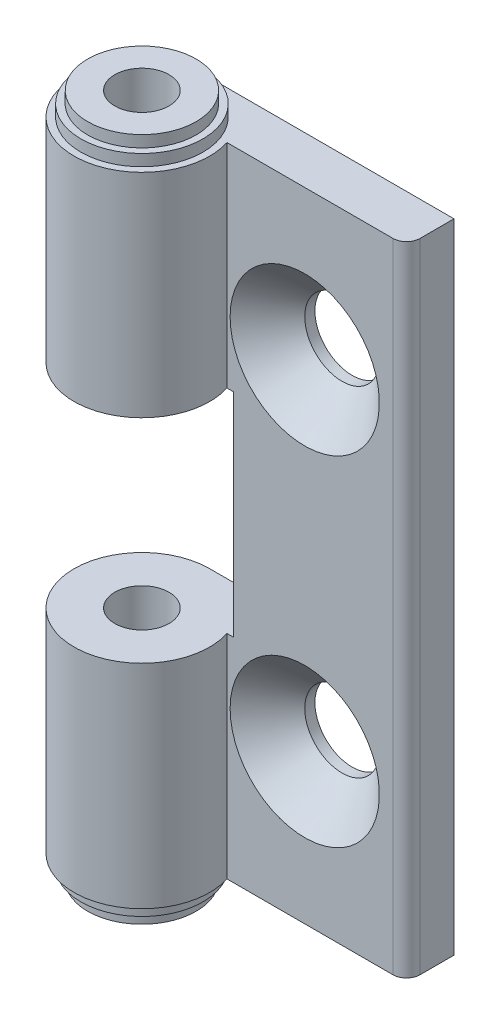
SolidWorks part; units mm, degrees
ref_plane "Front Plane" through (0, 0, 0) normal (0, 0, 1) x (1, 0, 0)
ref_plane "Top Plane" through (0, 0, 0) normal (0, 1, 0) x (1, 0, 0)
ref_plane "Right Plane" through (0, 0, 0) normal (1, 0, 0) x (0, 0, -1)
ref_plane "Plane1" through (0, 0, 0) normal (0, 0, 1) x (1, 0, 0)
sketch "Sketch1" plane through (0, 0, 0) normal (0, 0, 1) x (1, 0, 0)
  line L0 (0, 23.5) -> (5, 23.5)
  line L1 (5, 23.5) -> (5, -23.5)
  line L2 (5, -23.5) -> (0, -23.5)
  line L3 (0, -23.5) -> (0, 23.5)
  line L4 (0, -23.5) -> (0, 23.5) construction
revolve "Revolve1" add sketch "Sketch1" angle 360 about L4 reverse direction yes
ref_plane "Plane2" through (0, 0, -5) normal (0, 0, 1) x (1, 0, 0)
sketch "Sketch2" plane through (0, 0, -5) normal (0, 0, 1) x (1, 0, 0)
  line L0 (0, -23.5) -> (18, -23.5)
  line L1 (18, -23.5) -> (18, 23.5)
  line L2 (18, 23.5) -> (0, 23.5)
  line L3 (0, 23.5) -> (0, -23.5)
extrude "Boss-Extrude1" add sketch "Sketch2" along normal blind 3.5
ref_plane "Plane3" through (0, 0, 0) normal (0, 0, 1) x (1, 0, 0)
sketch "Sketch3" plane through (0, 0, 0) normal (0, 0, 1) x (1, 0, 0)
  line L0 (-47, -47) -> (47, -47)
  line L1 (47, -47) -> (47, 47)
  line L2 (47, 47) -> (-47, 47)
  line L3 (-47, 47) -> (-47, -47)
  line L4 (-5, 7.8333) -> (5.25, 7.8333)
  line L5 (5.25, 7.8333) -> (5.25, -7.8333)
  line L6 (5.25, -7.8333) -> (-5, -7.8333)
  line L7 (-5, -7.8333) -> (-5, -23.5)
  line L8 (-5, -23.5) -> (18, -23.5)
  line L9 (18, -23.5) -> (18, 23.5)
  line L10 (18, 23.5) -> (-5, 23.5)
  line L11 (-5, 23.5) -> (-5, 7.8333)
extrude "Cut-Extrude1" cut sketch "Sketch3" against normal blind 47 and the other way blind 47
ref_plane "Plane4" through (0, 0, 0) normal (0, 0, 1) x (1, 0, 0)
sketch "Sketch4" plane through (0, 0, 0) normal (0, 0, 1) x (1, 0, 0)
  line L0 (0, 25.2) -> (4, 25.2)
  line L1 (4, 25.2) -> (4, 24.35)
  line L2 (4, 24.35) -> (4.5, 24.35)
  line L3 (4.5, 24.35) -> (4.5, 23.5)
  line L4 (4.5, 23.5) -> (0, 23.5)
  line L5 (0, 23.5) -> (0, 25.2)
  line L6 (0, 23.5) -> (0, 25.2) construction
revolve "Revolve2" add sketch "Sketch4" angle 360 about L6 reverse direction yes
ref_plane "Plane5" through (0, 0, 0) normal (0, 0, 1) x (1, 0, 0)
sketch "Sketch5" plane through (0, 0, 0) normal (0, 0, 1) x (1, 0, 0)
  line L0 (0, -23.5) -> (4.5, -23.5)
  line L1 (4.5, -23.5) -> (4.5, -24.35)
  line L2 (4.5, -24.35) -> (4, -24.35)
  line L3 (4, -24.35) -> (4, -25.2)
  line L4 (4, -25.2) -> (0, -25.2)
  line L5 (0, -25.2) -> (0, -23.5)
  line L6 (0, -25.2) -> (0, -23.5) construction
revolve "Revolve3" add sketch "Sketch5" angle 360 about L6 reverse direction yes
ref_plane "Plane6" through (0, 0, 0) normal (0, 0, 1) x (1, 0, 0)
sketch "Sketch6" plane through (0, 0, 0) normal (0, 0, 1) x (1, 0, 0)
  line L0 (0, 26.7) -> (2, 26.7)
  line L1 (2, 26.7) -> (2, -26.7)
  line L2 (2, -26.7) -> (0, -26.7)
  line L3 (0, -26.7) -> (0, 26.7)
  line L4 (0, -26.7) -> (0, 26.7) construction
revolve "Cut-Revolve1" cut sketch "Sketch6" angle 360 about L4 reverse direction yes
ref_plane "Plane7" through (10.5, 0, 0) normal (1, 0, 0) x (0, 0, -1)
sketch "Sketch7" plane through (10.5, 0, 0) normal (1, 0, 0) x (0, 0, -1)
  line L0 (5, -12.5) -> (5, -15.25)
  line L1 (5, -15.25) -> (4.25, -15.25)
  line L2 (4.25, -15.25) -> (1.5, -18)
  line L3 (1.5, -18) -> (1.5, -12.5)
  line L4 (1.5, -12.5) -> (5, -12.5)
  line L5 (1.5, -12.5) -> (5, -12.5) construction
revolve "Cut-Revolve2" cut sketch "Sketch7" angle 360 about L5 reverse direction yes
ref_plane "Plane8" through (10.5, 0, 0) normal (1, 0, 0) x (0, 0, -1)
sketch "Sketch8" plane through (10.5, 0, 0) normal (1, 0, 0) x (0, 0, -1)
  line L0 (5, 12.5) -> (5, 9.75)
  line L1 (5, 9.75) -> (4.25, 9.75)
  line L2 (4.25, 9.75) -> (1.5, 7)
  line L3 (1.5, 7) -> (1.5, 12.5)
  line L4 (1.5, 12.5) -> (5, 12.5)
  line L5 (1.5, 12.5) -> (5, 12.5) construction
revolve "Cut-Revolve3" cut sketch "Sketch8" angle 360 about L5 reverse direction yes
ref_plane "Plane9" through (0, 0, 0) normal (0, 1, 0) x (1, 0, 0)
sketch "Sketch9" plane through (0, 0, 0) normal (0, 1, 0) x (1, 0, 0)
  line L0 (17, 1.5) -> (18, 1.5)
  line L1 (18, 1.5) -> (18, 2.5)
  arc A0 (18, 2.5) -> (17, 1.5) centre (17, 2.5) cw
extrude "Cut-Extrude2" cut sketch "Sketch9" against normal blind 23.5 and the other way blind 23.5
